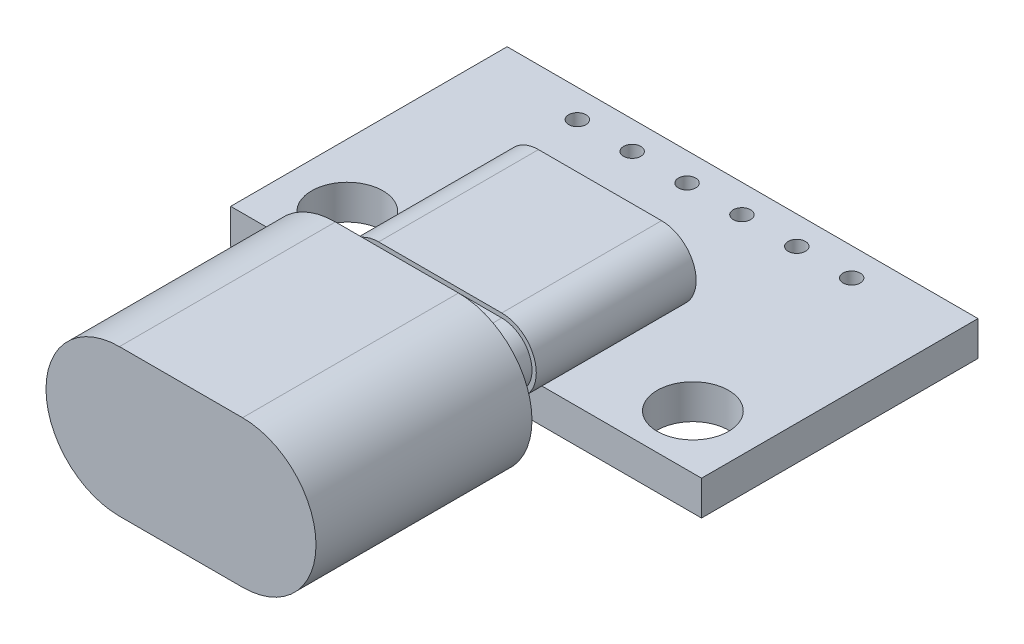
SolidWorks part; units mm, degrees
ref_plane "Front Plane" through (0, 0, 0) normal (0, 0, 1) x (1, 0, 0)
ref_plane "Top Plane" through (0, 0, 0) normal (0, 1, 0) x (1, 0, 0)
ref_plane "Right Plane" through (0, 0, 0) normal (1, 0, 0) x (0, 0, -1)
sketch "Sketch1" plane through (0, 0, 0) normal (0, 1, 0) x (1, 0, 0)
  line L1 (-10.9, -6.4) -> (10.9, -6.4)
  line L2 (-10.9, -6.4) -> (-10.9, 6.4)
  line L3 (-10.9, 6.4) -> (10.9, 6.4)
  line L4 (10.9, -6.4) -> (10.9, 6.4)
  line L5 (-10.9, -6.4) -> (10.9, 6.4) construction
  line L6 (-10.9, 6.4) -> (10.9, -6.4) construction
  point P0 (0, 0)
  dimension "D1" = 12.8
  dimension "D2" = 21.8
extrude "Boss-Extrude1" add sketch "Sketch1" along normal blind 1.6
sketch "Sketch2" plane through (0, 1.6, 0) normal (0, 1, 0) x (1, 0, 0)
  line L0 (-10.9, -3.9) -> (10.9, -3.9) construction
  line L1 (-10.9, 6.4) -> (-10.9, -6.4) construction
  line L2 (10.9, -6.4) -> (10.9, 6.4) construction
  line L3 (-10.9, -6.4) -> (10.9, -6.4) construction
  line L4 (-8, -3.9) -> (0, 0) construction
  line L5 (0, 0) -> (8, -3.9) construction
  circle A0 centre (-8, -3.9) radius 1.65
  circle A1 centre (8, -3.9) radius 1.65
  dimension "D1" = 3.3
  dimension "D2" = 16
  dimension "D3" = 2.5
extrude "Cut-Extrude1" cut sketch "Sketch2" against normal blind 1.6
ref_plane "Plane1" through (0, 0, 7.6) normal (0, 0, 1) x (1, 0, 0)
sketch "Sketch3" plane through (0, 0, 7.6) normal (0, 0, 1) x (1, 0, 0)
  line L0 (0, 0) -> (0, 3.2) construction
  line L1 (-2.85, 3.2) -> (2.85, 3.2) construction
  line L2 (-2.85, 4.8) -> (2.85, 4.8)
  line L3 (-2.85, 1.6) -> (2.85, 1.6)
  line L4 (-10.9, 1.6) -> (10.9, 1.6) construction
  arc A0 (-2.85, 4.8) -> (-2.85, 1.6) centre (-2.85, 3.2) ccw
  arc A1 (2.85, 1.6) -> (2.85, 4.8) centre (2.85, 3.2) ccw
  point P5 (0, 3.2)
  dimension "D1" = 8.9
  dimension "D2" = 3.2
extrude "Boss-Extrude2" add sketch "Sketch3" against normal blind 7.4
sketch "Sketch4" plane through (0, 0, 7.6) normal (0, 0, 1) x (1, 0, 0)
  line L4 (-2.85, 1.8) -> (2.85, 1.8)
  line L5 (2.85, 4.6) -> (-2.85, 4.6)
  line L6 (-2.85, 1.8) -> (2.85, 1.8)
  line L7 (2.85, 4.6) -> (-2.85, 4.6)
  arc A4 (-2.85, 4.6) -> (-2.85, 1.8) centre (-2.85, 3.2) ccw
  arc A5 (2.85, 1.8) -> (2.85, 4.6) centre (2.85, 3.2) ccw
  arc A6 (-2.85, 4.6) -> (-2.85, 1.8) centre (-2.85, 3.2) ccw
  arc A7 (2.85, 1.8) -> (2.85, 4.6) centre (2.85, 3.2) ccw
  dimension "D1" = 0.2
extrude "Boss-Extrude3" add sketch "Sketch4" along normal blind 2
sketch "Sketch5" plane through (0, 0, 9.6) normal (0, 0, 1) x (1, 0, 0)
  line L4 (-2.85, -0.2) -> (2.85, -0.2)
  line L5 (2.85, 6.6) -> (-2.85, 6.6)
  line L6 (-2.85, -0.2) -> (2.85, -0.2)
  line L7 (2.85, 6.6) -> (-2.85, 6.6)
  arc A4 (-2.85, 6.6) -> (-2.85, -0.2) centre (-2.85, 3.2) ccw
  arc A5 (2.85, -0.2) -> (2.85, 6.6) centre (2.85, 3.2) ccw
  arc A6 (-2.85, 6.6) -> (-2.85, -0.2) centre (-2.85, 3.2) ccw
  arc A7 (2.85, -0.2) -> (2.85, 6.6) centre (2.85, 3.2) ccw
  dimension "D3" = 12.5
  dimension "D2" = 6.8
  dimension "D1" = 2
extrude "Boss-Extrude4" add sketch "Sketch5" along normal blind 10
split "Split1" bodies to split 105 resulting bodies 106 107 split by face at (0, 3.2, 7.6)
sketch "Sketch6" plane through (0, 0, 7.6) normal (0, 0, 1) x (1, 0, 0)
  line L7 (-2.85, 1.9) -> (2.85, 1.9)
  line L8 (2.85, 4.5) -> (-2.85, 4.5)
  line L9 (-2.85, 1.9) -> (2.85, 1.9)
  line L10 (2.85, 4.5) -> (-2.85, 4.5)
  arc A8 (-2.85, 4.5) -> (-2.85, 1.9) centre (-2.85, 3.2) ccw
  arc A9 (2.85, 1.9) -> (2.85, 4.5) centre (2.85, 3.2) ccw
  arc A10 (-2.85, 4.5) -> (-2.85, 1.9) centre (-2.85, 3.2) ccw
  arc A11 (2.85, 1.9) -> (2.85, 4.5) centre (2.85, 3.2) ccw
  dimension "D1" = 0.3
extrude "Cut-Extrude2" cut sketch "Sketch6" against normal blind 6
sketch "Sketch7" plane through (0, 0, 1.6) normal (0, 0, 1) x (1, 0, 0)
  line L0 (-4.15, 3.2) -> (4.15, 3.2) construction
  line L2 (-2.9, 2.85) -> (2.9, 2.85)
  line L3 (-2.9, 2.85) -> (-2.9, 3.55)
  line L4 (-2.9, 3.55) -> (2.9, 3.55)
  line L5 (2.9, 2.85) -> (2.9, 3.55)
  line L6 (-2.9, 2.85) -> (2.9, 3.55) construction
  line L7 (-2.9, 3.55) -> (2.9, 2.85) construction
  arc A0 (-2.85, 4.5) -> (-2.85, 1.9) centre (-2.85, 3.2) ccw construction
  arc A1 (2.85, 1.9) -> (2.85, 4.5) centre (2.85, 3.2) ccw construction
  point P8 (0, 3.2)
  dimension "D1" = 0.7
  dimension "D2" = 5.8
extrude "Boss-Extrude5" add sketch "Sketch7" along normal offset from surface (5 mm away) 1 up to face at (0, 3.2, 7.6)
sketch "Sketch8" plane through (0, 1.6, 0) normal (0, 1, 0) x (1, 0, 0)
  line L0 (0, 0) -> (0, 6.4) construction
  line L1 (10.9, 6.4) -> (-10.9, 6.4) construction
  line L2 (-6.35, 5.1) -> (-3.81, 5.1) construction
  line L3 (-3.81, 5.1) -> (-1.27, 5.1) construction
  line L4 (-1.27, 5.1) -> (0, 5.1) construction
  circle A0 centre (-1.27, 5.1) radius 0.4
  circle A1 centre (-3.81, 5.1) radius 0.4
  circle A2 centre (-6.35, 5.1) radius 0.4
  circle A3 centre (1.27, 5.1) radius 0.4
  circle A4 centre (3.81, 5.1) radius 0.4
  circle A5 centre (6.35, 5.1) radius 0.4
  dimension "D1" = 1.27
  dimension "D4" = 0.8
  dimension "D2" = 2.54
  dimension "D3" = 2.54
  dimension "D5" = 1.3
extrude "Cut-Extrude3" cut sketch "Sketch8" against normal through all
